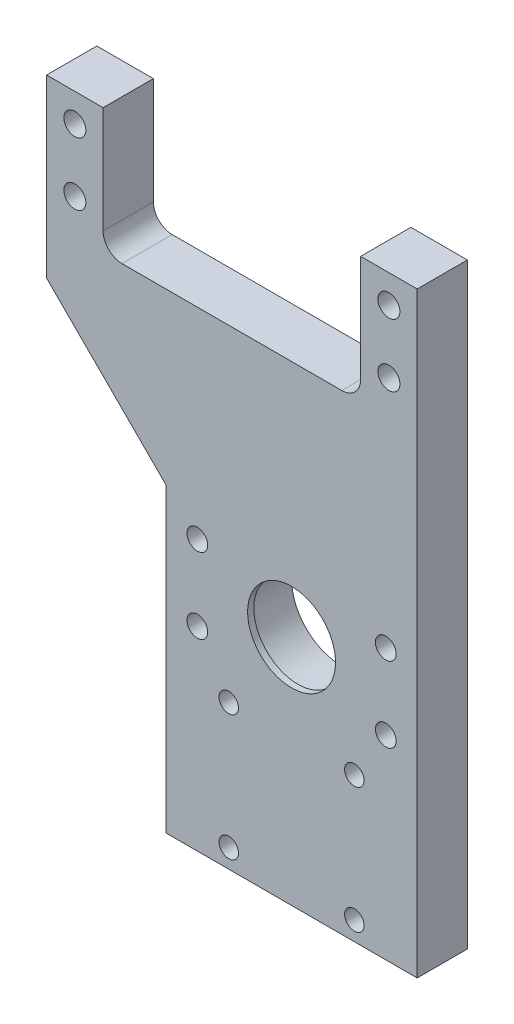
SolidWorks part; units mm, degrees
ref_plane "Front" through (0, 0, 0) normal (0, 0, 1) x (1, 0, 0)
ref_plane "Top" through (0, 0, 0) normal (0, 1, 0) x (1, 0, 0)
ref_plane "Right" through (0, 0, 0) normal (1, 0, 0) x (0, 0, -1)
sketch "Esquisse1" plane through (0, 0, 0) normal (0, 0, 1) x (1, 0, 0)
  line L1 (0, 0) -> (40, 0)
  line L2 (0, 0) -> (0, 30)
  line L3 (0, 30) -> (40, 30)
  line L4 (40, 0) -> (40, 30)
  dimension "D1" = 40
  dimension "D2" = 30
extrude "Boss.-Extru.1" add sketch "Esquisse1" along normal blind 8
sketch "Esquisse2" plane through (0, 0, 8) normal (0, 0, 1) x (1, 0, 0)
  line L0 (20, 15) -> (20, 0) construction
  line L1 (0, 0) -> (40, 0) construction
  line L2 (0, 15) -> (20, 15) construction
  line L3 (0, 30) -> (0, 0) construction
  circle A0 centre (20, 15) radius 8
  dimension "D1" = 16
extrude "Enlèv. mat.-Extru.1" cut sketch "Esquisse2" along normal blind 7 from vertex at -8 starting at point (40, 30, 0)
sketch "Esquisse3" plane through (0, 0, 8) normal (0, 0, 1) x (1, 0, 0)
  line L0 (40, 0) -> (40, 30) construction
  line L1 (0, 0) -> (40, 0)
  line L2 (0, 0) -> (0, -22)
  line L3 (0, -22) -> (40, -22)
  line L4 (40, 0) -> (40, -22)
  dimension "D1" = 22
extrude "Boss.-Extru.2" add sketch "Esquisse3" against normal up to vertex (8 mm away) up to point (40, 0, 0)
sketch "Esquisse4" plane through (0, 0, 8) normal (0, 0, 1) x (1, 0, 0)
  line L0 (20, -22) -> (20, 4) construction
  line L1 (0, -22) -> (40, -22) construction
  line L2 (20, -9) -> (30.0882, -9) construction
  circle A0 centre (30, -19) radius 1.55
  circle A1 centre (30, 1) radius 1.55
  circle A2 centre (10, 1) radius 1.55
  circle A3 centre (10, -19) radius 1.55
  dimension "D1" = 20
  dimension "D2" = 20
  dimension "D3" = 3.1
  dimension "D4" = 26
extrude "Enlèv. mat.-Extru.2" cut sketch "Esquisse4" against normal up to vertex
sketch "Esquisse5" plane through (0, 0, 8) normal (0, 0, 1) x (1, 0, 0)
  line L0 (40, -22) -> (40, 30) construction
  line L1 (0, 30) -> (40, 30)
  line L2 (0, 30) -> (0, 73)
  line L3 (0, 73) -> (40, 73)
  line L4 (40, 30) -> (40, 73)
  dimension "D1" = 43
extrude "Boss.-Extru.3" add sketch "Esquisse5" against normal up to vertex (8 mm away)
sketch "Esquisse6" plane through (0, 0, 8) normal (0, 0, 1) x (1, 0, 0)
  line L0 (40, -22) -> (40, 73) construction
  line L1 (0, 73) -> (31, 73)
  line L2 (0, 73) -> (0, 53)
  line L3 (0, 53) -> (31, 53)
  line L4 (31, 73) -> (31, 53)
  dimension "D1" = 20
  dimension "D2" = 9
extrude "Enlèv. mat.-Extru.3" cut sketch "Esquisse6" against normal up to vertex
sketch "Esquisse7" plane through (0, 0, 8) normal (0, 0, 1) x (1, 0, 0)
  line L0 (0, 53) -> (-10, 53)
  line L1 (-10, 53) -> (-10, 73)
  line L2 (-10, 73) -> (-19, 73)
  line L3 (-19, 73) -> (-19, 45)
  line L4 (-19, 45) -> (0, 45)
  line L5 (0, 53) -> (0, -22) construction
  line L6 (0, 45) -> (0, 53)
  line L7 (31, 53) -> (31, 73) construction
  line L8 (40, 73) -> (31, 73) construction
  dimension "D1" = 8
  dimension "D2" = 9
  dimension "D3" = 41
extrude "Boss.-Extru.4" add sketch "Esquisse7" against normal up to vertex (8 mm away)
sketch "Esquisse8" plane through (0, 0, 8) normal (0, 0, 1) x (1, 0, 0)
  line L0 (35.5, 73) -> (35.5, 54) construction
  line L1 (40, 73) -> (31, 73) construction
  line L2 (35.5, 63.5) -> (37.0128, 63.5) construction
  line L3 (10.5, 53) -> (10.5, 68.2235) construction
  line L4 (-10, 53) -> (31, 53) construction
  circle A0 centre (35.5, 58.5) radius 1.75
  circle A1 centre (35.5, 68.5) radius 1.75
  circle A2 centre (-14.5, 68.5) radius 1.75
  circle A3 centre (-14.5, 58.5) radius 1.75
  dimension "D1" = 10
  dimension "D2" = 3.5
  dimension "D3" = 50
  dimension "D4" = 10.5
extrude "Enlèv. mat.-Extru.4" cut sketch "Esquisse8" against normal through all
sketch "Esquisse9" plane through (0, 0, 7) normal (0, 0, -1) x (-1, 0, 0)
  circle A0 centre (-20, 15) radius 7
  dimension "D1" = 14
extrude "Enlèv. mat.-Extru.5" cut sketch "Esquisse9" against normal through all
sketch "Esquisse10" plane through (0, -22, 0) normal (0, -1, 0) x (-1, 0, 0)
  line L0 (-40, -4) -> (-20, -4) construction
  line L1 (-40, 0) -> (-40, -8) construction
  circle A0 centre (-20, -4) radius 1.65
  circle A1 centre (-36, -4) radius 1.65
  dimension "D1" = 3.3
  dimension "D2" = 16
  dimension "D3" = 4
extrude "Enlèv. mat.-Extru.6" cut sketch "Esquisse10" against normal blind 10
sketch "Esquisse11" plane through (0, 0, 0) normal (0, 0, -1) x (-1, 0, 0)
  line L0 (-20, 15) -> (-35, 15) construction
  line L1 (-35, 15) -> (-35, 21) construction
  line L2 (-20, 15) -> (-20, 18.1299) construction
  circle A0 centre (-35, 21) radius 1.65
  circle A1 centre (-5, 21) radius 1.65
  circle A2 centre (-5, 9) radius 1.65
  circle A3 centre (-35, 9) radius 1.65
  dimension "D1" = 3.3
  dimension "D2" = 12
  dimension "D3" = 30
extrude "Enlèv. mat.-Extru.7" cut sketch "Esquisse11" against normal through all
chamfer "Chanfrein1" distance 19 angle 45 1 edges at (0, 45, 4)
fillet "Congé1" radius 3 2 edges at (-10, 53, 4) (31, 53, 4)
